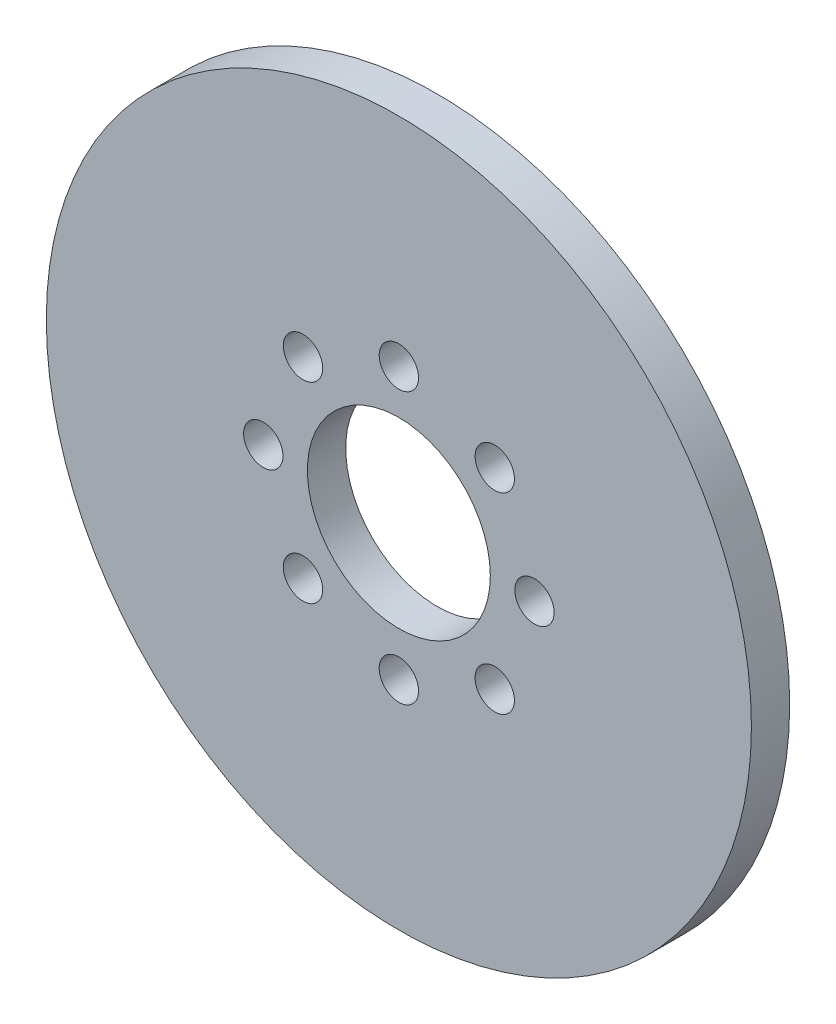
SolidWorks part; units mm, degrees
material "AISI Type A2 Tool Steel"
ref_plane "Front Plane" through (0, 0, 0) normal (0, 0, 1) x (1, 0, 0)
ref_plane "Top Plane" through (0, 0, 0) normal (0, 1, 0) x (1, 0, 0)
ref_plane "Right Plane" through (0, 0, 0) normal (1, 0, 0) x (0, 0, -1)
sketch "Sketch1" plane through (0, 0, 0) normal (0, 0, 1) x (1, 0, 0)
  line L0 (0, 0) -> (0, 22.5) construction
  line L1 (0, 0) -> (-39.3193, 27.5317) construction
  line L2 (0, 0) -> (39.3193, 27.5317) construction
  line L3 (-39.3193, 27.5317) -> (-22.9363, 16.0601)
  line L4 (39.3193, 27.5317) -> (22.9363, 16.0601)
  line L5 (43.5028, 20.2857) -> (25.3766, 11.8333)
  line L6 (4.1835, -47.8173) -> (2.4404, -27.8935)
  line L7 (-4.1835, -47.8173) -> (-2.4404, -27.8935)
  line L8 (-43.5028, 20.2857) -> (-25.3766, 11.8333)
  circle A0 centre (0, 0) radius 58.5
  circle A1 centre (0, 0) radius 22.5 construction
  circle A2 centre (0, 22.5) radius 3.2639
  circle A3 centre (15.9099, 15.9099) radius 3.2639
  circle A4 centre (22.5, 0) radius 3.2639
  circle A5 centre (15.9099, -15.9099) radius 3.2639
  circle A6 centre (0, -22.5) radius 3.2639
  circle A7 centre (-15.9099, -15.9099) radius 3.2639
  circle A8 centre (-22.5, 0) radius 3.2639
  circle A9 centre (-15.9099, 15.9099) radius 3.2639
  arc A10 (-39.3193, 27.5317) -> (39.3193, 27.5317) centre (0, 0) cw
  arc A11 (-22.9363, 16.0601) -> (22.9363, 16.0601) centre (0, 0) cw
  arc A12 (43.5028, 20.2857) -> (4.1835, -47.8173) centre (0, 0) cw
  arc A13 (25.3766, 11.8333) -> (2.4404, -27.8935) centre (0, 0) cw
  arc A14 (-4.1835, -47.8173) -> (-43.5028, 20.2857) centre (0, 0) cw
  arc A15 (-2.4404, -27.8935) -> (-25.3766, 11.8333) centre (0, 0) cw
  circle A16 centre (0, 0) radius 15.175
  point P4 (0, 22.5)
  point P8 (15.9099, 15.9099)
  point P9 (22.5, 0)
  point P10 (15.9099, -15.9099)
  point P11 (0, -22.5)
  point P12 (-15.9099, -15.9099)
  point P13 (-22.5, 0)
  point P14 (-15.9099, 15.9099)
  point P15 (0, 0)
  point P43 (0, 0)
  dimension "D1" = 117
  dimension "D2" = 45
  dimension "D4" = 6.5278
  dimension "D6" = 28
  dimension "D7" = 20
  dimension "D9" = 30.35
  dimension "D5" = 110
  dimension "D3" = 8
  dimension "D8" = 3
extrude "Boss-Extrude1" add sketch "Sketch1" along normal blind 6.35 contours L7 A15 L8 A14 | L3 A11 L4 A10 | L5 A13 L6 A12 | A0 A16 A15 L7 A14 L8 A13 L5 A12 L6 A11 L3 A10 L4 A9 A8 A7 A6 A5 A4 A3 A2 region at (0, 33.1756, 0) region at (28.731, -16.5878, 0) region at (-28.731, -16.5878, 0) region at (-56.8454, 0, 0)
